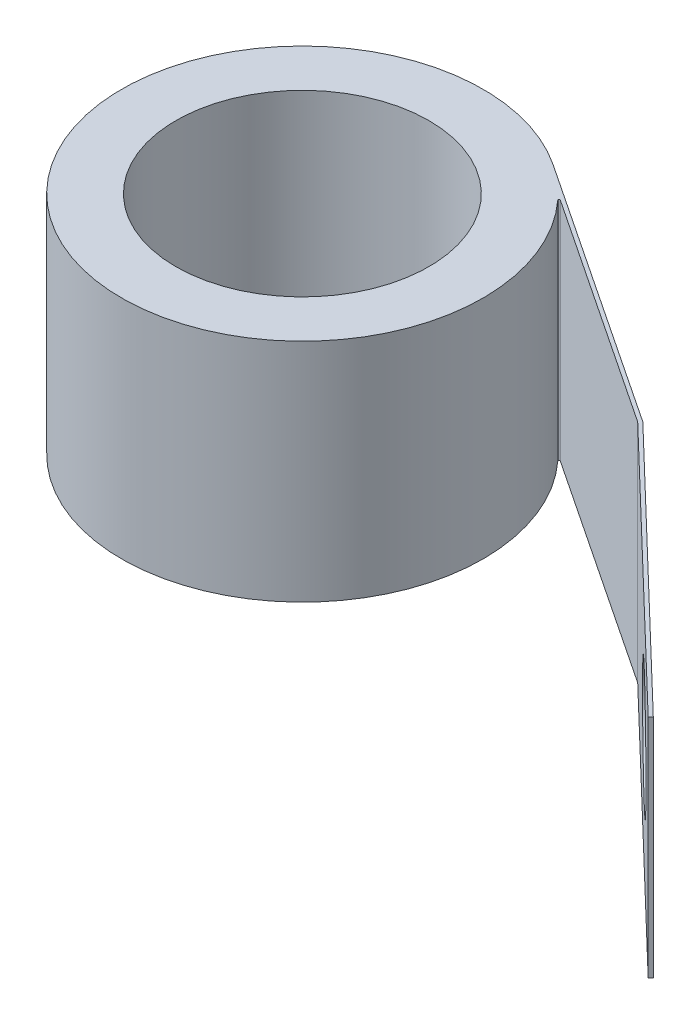
SolidWorks part; units mm, degrees
ref_plane "Front Plane" through (0, 0, 0) normal (0, 0, 1) x (1, 0, 0)
ref_plane "Top Plane" through (0, 0, 0) normal (0, 1, 0) x (1, 0, 0)
ref_plane "Right Plane" through (0, 0, 0) normal (1, 0, 0) x (0, 0, -1)
sketch "Sketch1" plane through (0, 0, 0) normal (0, 1, 0) x (1, 0, 0)
  line L0 (10.335, -0.7694) -> (2.8119, 4.2308)
  line L1 (10.2646, -0.8427) -> (3.5919, 3.5923)
  line L3 (17.5946, -7.8781) -> (10.2646, -0.8427)
  line L4 (11.2963, -1.8329) -> (18.5108, -8.7576) construction
  line L5 (17.6649, -7.8048) -> (10.335, -0.7694)
  line L6 (17.6649, -7.8048) -> (17.5946, -7.8781)
  circle A0 centre (0, 0) radius 3.556
  circle A1 centre (0, 0) radius 5.08
  dimension "D1" = 7.112
  dimension "D2" = 10.16
  dimension "D4" = 0.1016
  dimension "D5" = 10.16
extrude "Boss-Extrude1" add sketch "Sketch1" along normal blind 6.35 contours A1 A0 | A1 L1 L3 L6 L5 L0 region at (13.9867, 0, 4.3009) region at (3.1268, 0, -3.8198)
sketch "Sketch2" plane through (3.8365, 0, -5.4681) normal (0.6925, 0, -0.7214) x (-0.7214, 0, -0.6925)
  line L1 (-19.1675, 6.35) -> (-19.1675, 0) construction
  circle A0 centre (-15.3575, 3.175) radius 1.651
  point P2 (-19.1675, 3.175)
  dimension "D1" = 3.302
  dimension "D2" = 3.81
extrude "Cut-Extrude1" cut sketch "Sketch2" against normal blind 6.35
fillet "Fillet1" radius 0.0254 1 edges at (3.5919, 3.175, -3.5923)
